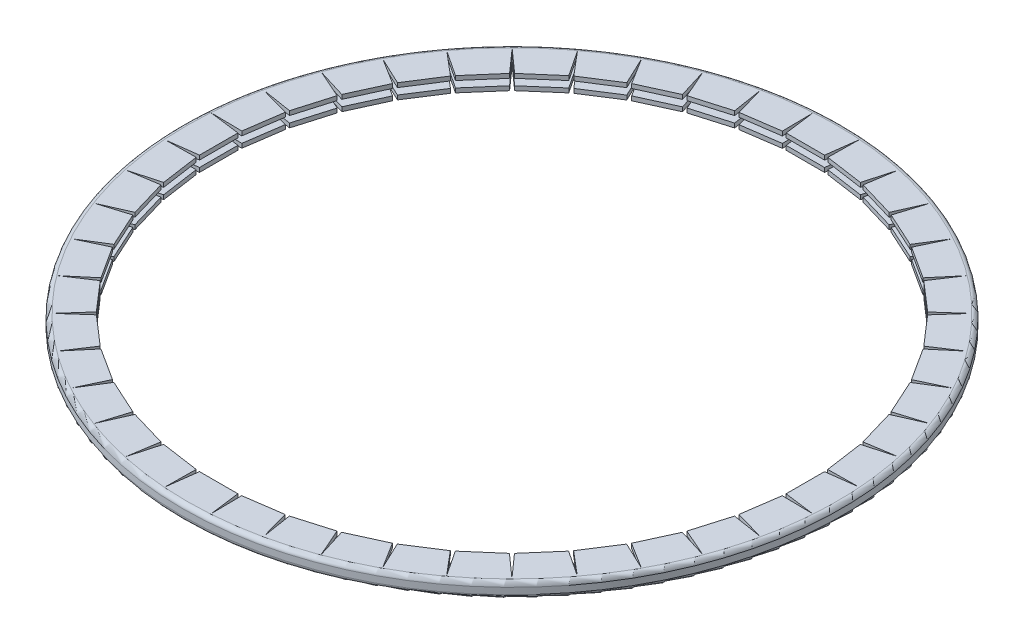
SolidWorks part; units mm, degrees
ref_plane "Front Plane" through (0, 0, 0) normal (0, 0, 1) x (1, 0, 0)
ref_plane "Top Plane" through (0, 0, 0) normal (0, 1, 0) x (1, 0, 0)
ref_plane "Right Plane" through (0, 0, 0) normal (1, 0, 0) x (0, 0, -1)
sketch "Sketch1" plane through (0, 0, 0) normal (0, 1, 0) x (1, 0, 0)
  circle A0 centre (0, 0) radius 244.475
  circle A1 centre (0, 0) radius 241.3
  dimension "D1" = 488.95
  dimension "D2" = 482.6
extrude "Boss-Extrude1" add sketch "Sketch1" along normal blind 11.1125
sketch "Sketch2" plane through (0, 0, 0) normal (0, 1, 0) x (1, 0, 0)
  line L2 (0, 0) -> (0, 386.7288) construction
  line L3 (-3.7465, 252.3652) -> (-3.7465, 199.5625)
  line L4 (-3.7465, 199.5625) -> (3.7465, 199.5625)
  line L5 (3.7465, 199.5625) -> (3.7465, 252.3652)
  line L6 (3.7465, 252.3652) -> (-3.7465, 252.3652)
  point P4 (0, 252.3652)
  dimension "D1" = 7.493
extrude "Cut-Extrude4" [suppressed] cut sketch "Sketch2" along normal through all contours L3 L4 L5 L6
sketch "Sketch3" plane through (0, 0, 0) normal (0, 1, 0) x (1, 0, 0)
  line L0 (-240.6829, 17.2466) -> (-217.5689, 14.224)
  line L1 (-217.5689, 14.224) -> (-217.5689, -14.224)
  line L2 (-217.5689, -14.224) -> (-240.6829, -17.2466)
  line L3 (0, 0) -> (-244.475, 0) construction
  line L4 (-217.5689, 14.224) -> (200.446, 14.224) construction
  line L5 (-244.475, 0) -> (-244.475, -61.6855) construction
  circle A0 centre (0, 0) radius 241.3 construction
  arc A1 (-240.6829, 17.2466) -> (-240.6829, -17.2466) centre (0, 0) ccw
  circle A2 centre (0, 0) radius 244.475 construction
  circle A3 centre (0, 0) radius 244.475 construction
  point P2 (-3.7465, 204.2939)
  point P3 (-217.5689, 0)
  point P10 (-14.1586, -244.0647)
  point P14 (-244.475, -61.6855)
  dimension "D1" = 3.0226
  dimension "D2" = 28.448
  dimension "D3" = 23.114
extrude "Boss-Extrude2" add sketch "Sketch3" along normal blind 11.1125
pattern_circular "CirPattern1" count 44 over 351.8 about axis through (0, 11.1125, 0) along (0, -1, 0) of "Boss-Extrude2" reverse direction yes
sketch "Sketch4" plane through (0, 0, 0) normal (1, 0, 0) x (0, 0, -1)
  line L0 (190.5, 7.9375) -> (241.3, 7.9375)
  line L1 (190.5, 7.9375) -> (190.5, 3.175)
  line L2 (241.3, 7.9375) -> (241.3, 3.175)
  line L3 (190.5, 3.175) -> (241.3, 3.175)
  line L4 (51.1302, 11.1125) -> (45.0063, 11.1125) construction
  line L5 (0, 0) -> (0, 46.4585) construction
  dimension "D1" = 3.175
  dimension "D2" = 241.3
  dimension "D3" = 4.7625
  dimension "D4" = 50.8
revolve "Cut-Revolve1" cut sketch "Sketch4" angle 360 about L5
fillet "Fillet1" radius 3.175 2 edges at (0, 0, 244.475) (0, 11.1125, 244.475)
